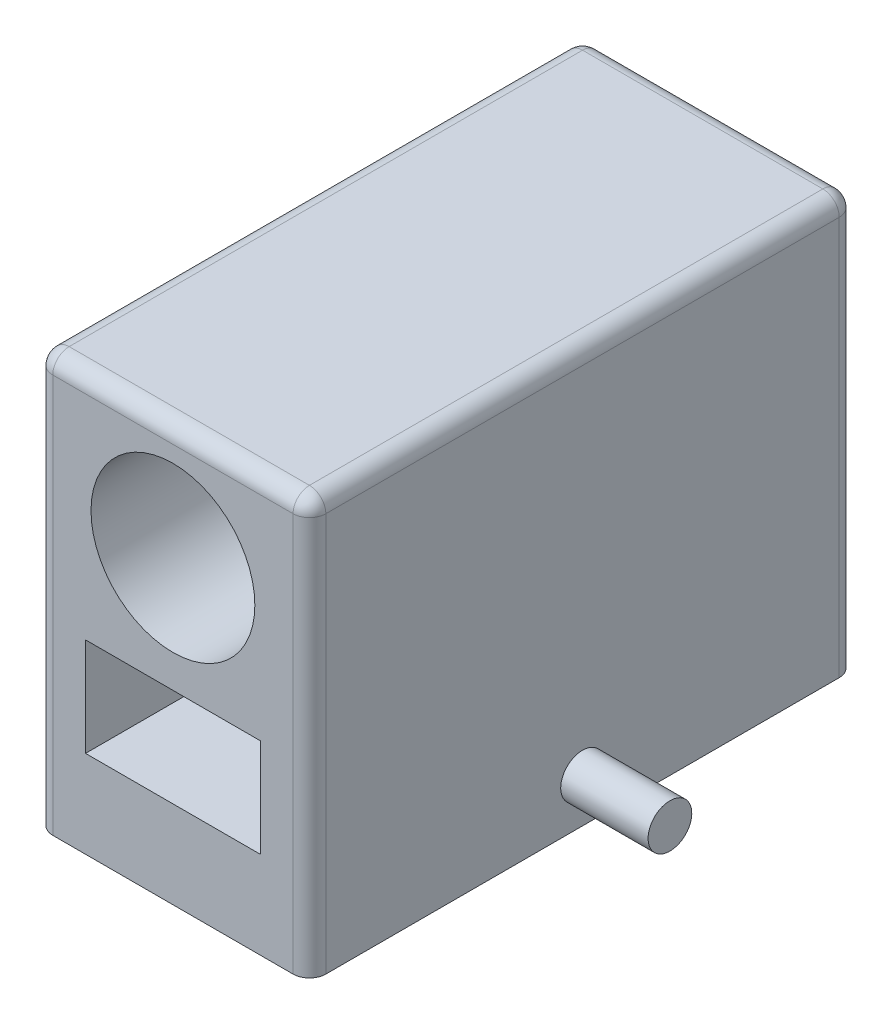
SolidWorks part; units mm, degrees
ref_plane "前视基准面" through (0, 0, 0) normal (0, 0, 1) x (1, 0, 0)
ref_plane "上视基准面" through (0, 0, 0) normal (0, 1, 0) x (1, 0, 0)
ref_plane "右视基准面" through (0, 0, 0) normal (1, 0, 0) x (0, 0, -1)
sketch "草图1" plane through (0, 0, 0) normal (0, 0, 1) x (1, 0, 0)
  line L0 (0, 0) -> (0, 38)
  line L1 (0, 38) -> (25, 38)
  line L2 (25, 38) -> (25, 0)
  line L3 (25, 0) -> (0, 0)
  dimension "D1" = 25
  dimension "D2" = 38
extrude "凸台-拉伸1" add sketch "草图1" against normal blind 50
sketch "草图2" plane through (0, 0, 0) normal (0, 0, 1) x (1, 0, 0)
  line L0 (-6.3321, 20) -> (48.7203, 20) construction
  line L1 (0, 0) -> (25, 0) construction
  line L2 (12.5, 47.0903) -> (12.5, -5.242) construction
  line L3 (25, 0) -> (25, 38) construction
  line L4 (5, 20) -> (5, 35) construction
  line L5 (5, 35) -> (20, 35) construction
  line L6 (20, 35) -> (20, 20) construction
  line L7 (20, 20) -> (5, 20) construction
  line L8 (5, 35) -> (20, 20) construction
  circle A0 centre (12.5, 27.5) radius 7.5
  dimension "D1" = 20
  dimension "D2" = 12.5
  dimension "D3" = 15
  dimension "D4" = 15
extrude "切除-拉伸1" cut sketch "草图2" against normal blind 13
ref_plane "基准面1" through (0, 0, -13) normal (0, 0, 1) x (1, 0, 0)
sketch "草图3" plane through (0, 0, -13) normal (0, 0, 1) x (1, 0, 0)
  line L0 (2, 0) -> (2, 36)
  line L1 (0, 0) -> (25, 0) construction
  line L2 (2, 36) -> (23, 36)
  line L3 (23, 36) -> (23, 0)
  line L4 (0, 38) -> (0, 0) construction
  line L5 (25, 38) -> (0, 38) construction
  line L6 (25, 0) -> (25, 38) construction
  line L7 (23, 0) -> (2, 0)
  dimension "D1" = 2
  dimension "D2" = 2
  dimension "D3" = 2
extrude "切除-拉伸2" cut sketch "草图3" against normal offset from surface (35 mm away) 2 up to face at (12.5, 19, -50)
ref_plane "基准面2" through (0, 0, -22) normal (0, 0, -1) x (-1, 0, 0)
sketch "草图4" plane through (2, 0, 0) normal (1, 0, 0) x (0, 0, -1)
  line L0 (22, 0) -> (22, 9)
  line L1 (22, -11.55) -> (22, 11.55) construction
  line L2 (50, 0) -> (0, 0) construction
  line L3 (22, 9) -> (38, 9)
  line L4 (38, 9) -> (38, 0)
  line L5 (38, 0) -> (22, 0)
  dimension "D1" = 16
  dimension "D2" = 9
extrude "切除-拉伸3" cut sketch "草图4" against normal blind 10
fillet "圆角1" radius 1.5 4 edges at (25, 38, -25) (12.5, 38, -50) (0, 38, -25) (12.5, 38, 0)
fillet "圆角2" radius 1.5 6 edges at (24.5607, 37.5607, -49.5607) (0.4393, 37.5607, -49.5607) (0.4393, 37.5607, -0.4393) (25, 18.25, -50) (0, 18.25, -50) (0, 18.25, 0)
fillet "圆角3" radius 1.5 2 edges at (24.5607, 37.5607, -0.4393) (25, 18.25, 0)
ref_plane "基准面3" through (-10, 0, 0) normal (-1, 0, 0) x (0, 0, 1)
sketch "草图5" plane through (25, 0, 0) normal (1, 0, 0) x (0, 0, -1)
  line L0 (25, 15.9775) -> (25, -3.9085) construction
  line L1 (38.3484, 4) -> (20.3543, 4) construction
  line L2 (22, -11.55) -> (22, 11.55) construction
  line L3 (48.5, 0) -> (1.5, 0) construction
  circle A0 centre (25, 4) radius 2
  dimension "D3" = 4
  dimension "D1" = 3
  dimension "D2" = 4
extrude "凸台-拉伸2" add sketch "草图5" along normal blind 8
sketch "草图6" plane through (0, 0, 0) normal (0, 0, 1) x (1, 0, 0)
  line L0 (12.5, 43.9411) -> (12.5, -5.9351) construction
  line L1 (25, 36.5) -> (25, 0) construction
  line L2 (-9.1561, 8) -> (35.3458, 8) construction
  line L3 (1.5, 0) -> (23.5, 0) construction
  line L4 (-9.1561, 17) -> (35.3458, 17) construction
  line L5 (4.5, -4.6627) -> (4.5, 26.2056) construction
  line L6 (20.5, 26.2056) -> (20.5, -4.6627) construction
  line L7 (4.5, 17) -> (4.5, 8)
  line L8 (4.5, 8) -> (20.5, 8)
  line L9 (20.5, 8) -> (20.5, 17)
  line L10 (20.5, 17) -> (4.5, 17)
  dimension "D1" = 12.5
  dimension "D2" = 8
  dimension "D3" = 9
  dimension "D4" = 16
extrude "切除-拉伸4" cut sketch "草图6" against normal up to next
